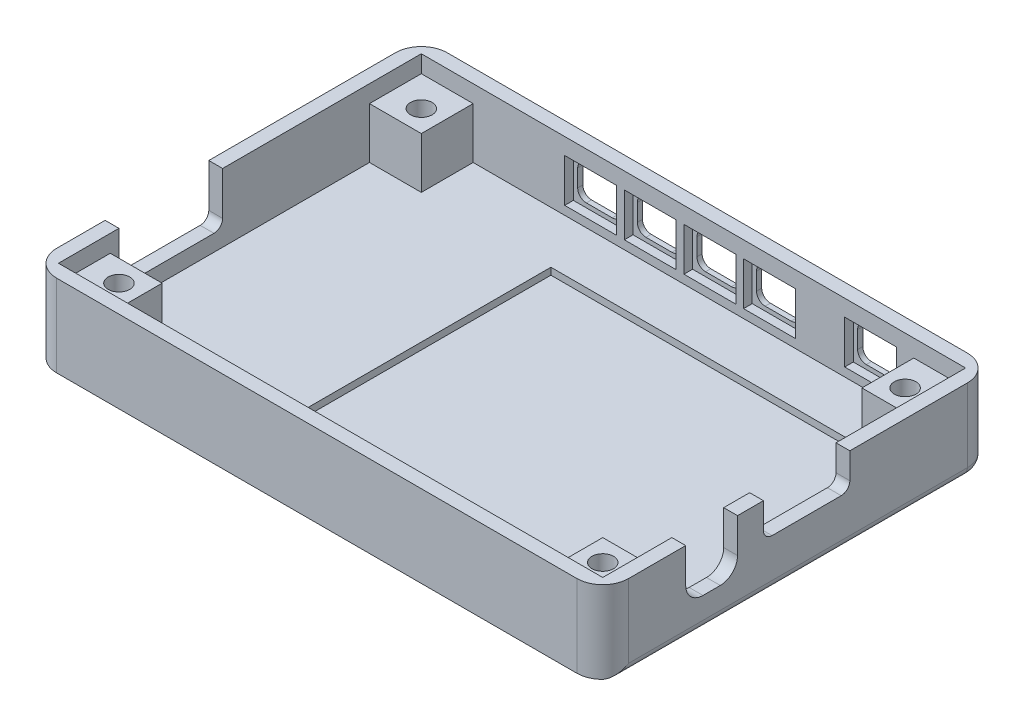
SolidWorks part; units mm, degrees
ref_plane "前视基准面" through (0, 0, 0) normal (0, 0, 1) x (1, 0, 0)
ref_plane "上视基准面" through (0, 0, 0) normal (0, 1, 0) x (1, 0, 0)
ref_plane "右视基准面" through (0, 0, 0) normal (1, 0, 0) x (0, 0, -1)
sketch "草图1" plane through (0, 0, 0) normal (0, 1, 0) x (1, 0, 0)
  line L1 (-31.5, -21) -> (31.5, -21)
  line L2 (-31.5, -21) -> (-31.5, 21)
  line L3 (-31.5, 21) -> (31.5, 21)
  line L4 (31.5, -21) -> (31.5, 21)
  line L5 (-31.5, -21) -> (31.5, 21) construction
  line L6 (-31.5, 21) -> (31.5, -21) construction
  point P0 (0, 0)
  dimension "D1" = 63
  dimension "D2" = 42
extrude "底" add sketch "草图1" against normal blind 1.6
sketch "草图2" plane through (0, 0, 0) normal (0, 1, 0) x (1, 0, 0)
  line L1 (-10.5, -15) -> (31.5, -15)
  line L2 (-10.5, -15) -> (-10.5, 15)
  line L3 (-10.5, 15) -> (31.5, 15)
  line L4 (31.5, -15) -> (31.5, 15)
  line L5 (-10.5, -15) -> (31.5, 15) construction
  line L6 (-10.5, 15) -> (31.5, -15) construction
  line L7 (31.5, 21) -> (-31.5, 21) construction
  line L8 (-31.5, -21) -> (31.5, -21) construction
  line L9 (31.5, -21) -> (31.5, 21) construction
  point P0 (0, 0)
  dimension "D1" = 42
  dimension "D2" = 6
  dimension "D3" = 0
  dimension "D4" = 6
extrude "电池槽" cut sketch "草图2" against normal blind 0.8
sketch "草图4" plane through (0, -1.6, 0) normal (0, -1, 0) x (-1, 0, 0)
  line L0 (-31.5, 21) -> (-31.5, -21)
  line L1 (-31.5, 21) -> (-33.1, 21)
  line L2 (-31.5, -21) -> (-33.1, -21)
  line L3 (-33.1, 21) -> (-33.1, -21)
  line L4 (31.5, 21) -> (31.5, -21)
  line L5 (31.5, 21) -> (33.1, 21)
  line L6 (31.5, -21) -> (33.1, -21)
  line L7 (33.1, 21) -> (33.1, -21)
  dimension "D1" = 1.6
  dimension "D2" = 1.6
extrude "侧边" add sketch "草图4" against normal blind 9.5
sketch "草图5" plane through (0, 0, 0) normal (0, 1, 0) x (1, 0, 0)
  line L0 (-31.5, 21) -> (-31.5, 15)
  line L1 (-31.5, 21) -> (-25.5, 21)
  line L2 (-31.5, 15) -> (-25.5, 15)
  line L3 (-25.5, 21) -> (-25.5, 15)
  line L4 (-31.5, 21) -> (-31.5, -21) construction
  line L5 (25.5, 21) -> (25.5, 15)
  line L6 (25.5, 21) -> (31.5, 21)
  line L7 (25.5, 15) -> (31.5, 15)
  line L8 (31.5, 21) -> (31.5, 15)
  line L9 (-31.5, -15) -> (-31.5, -21)
  line L10 (-31.5, -15) -> (-25.5, -15)
  line L11 (-31.5, -21) -> (-25.5, -21)
  line L12 (-25.5, -15) -> (-25.5, -21)
  line L13 (25.5, -15) -> (25.5, -21)
  line L14 (25.5, -15) -> (31.5, -15)
  line L15 (25.5, -21) -> (31.5, -21)
  line L16 (31.5, -15) -> (31.5, -21)
  dimension "D1" = 6
  dimension "D2" = 6
  dimension "D3" = 6
  dimension "D4" = 6
extrude "螺丝固定" add sketch "草图5" along normal offset from surface (5.9 mm away) 2 up to face at (-32.3, 7.9, 0)
sketch "草图6" plane through (0, 7.9, 0) normal (0, 1, 0) x (1, 0, 0)
  line L0 (-25.5, 15) -> (-25.5, 21) construction
  line L1 (-31.5, 15) -> (-25.5, 15) construction
  circle A0 centre (-28, 17.5) radius 1.25
  circle A1 centre (28, 17.5) radius 1.25
  circle A2 centre (28, -17.5) radius 1.25
  circle A3 centre (-28, -17.5) radius 1.25
  dimension "D1" = 2.5
  dimension "D2" = 2.5
  dimension "D3" = 2.5
  dimension "D4" = 2
  dimension "D5" = 2
extrude "螺丝孔" cut sketch "草图6" against normal up to surface (7.9 mm away) up to face at (-7, 0, 0)
sketch "草图8" plane through (0, 0, 0) normal (0, 1, 0) x (1, 0, 0)
  line L0 (25.5, 21) -> (25.5, 15) construction
  line L1 (-30.5, 20) -> (-25.5, 20)
  line L2 (-30.5, 20) -> (-30.5, 15)
  line L3 (-30.5, 15) -> (-25.5, 15)
  line L4 (-25.5, 20) -> (-25.5, 15)
  line L5 (-30.5, 20) -> (-25.5, 15) construction
  line L6 (-30.5, 15) -> (-25.5, 20) construction
  line L7 (30.5, 20) -> (25.5, 20)
  line L8 (30.5, 20) -> (30.5, 15)
  line L9 (30.5, 15) -> (25.5, 15)
  line L10 (25.5, 20) -> (25.5, 15)
  line L11 (30.5, 20) -> (25.5, 15) construction
  line L12 (30.5, 15) -> (25.5, 20) construction
  line L14 (-30.5, -20) -> (-25.5, -20)
  line L15 (-30.5, -20) -> (-30.5, -15)
  line L16 (-30.5, -15) -> (-25.5, -15)
  line L17 (-25.5, -20) -> (-25.5, -15)
  line L18 (-30.5, -20) -> (-25.5, -15) construction
  line L19 (-30.5, -15) -> (-25.5, -20) construction
  line L20 (30.5, -20) -> (25.5, -20)
  line L21 (30.5, -20) -> (30.5, -15)
  line L22 (30.5, -15) -> (25.5, -15)
  line L23 (25.5, -20) -> (25.5, -15)
  line L24 (30.5, -20) -> (25.5, -15) construction
  line L25 (30.5, -15) -> (25.5, -20) construction
  circle A0 centre (28, 17.5) radius 1.25 construction
  circle A1 centre (28, -17.5) radius 1.25 construction
  circle A2 centre (-28, -17.5) radius 1.25 construction
  circle A3 centre (-28, 17.5) radius 1.25 construction
  circle A4 centre (28, 17.5) radius 1.25 construction
  circle A5 centre (28, -17.5) radius 1.25 construction
  circle A6 centre (-28, -17.5) radius 1.25 construction
  circle A7 centre (-28, 17.5) radius 1.25 construction
sketch "草图9" plane through (0, 0, -21) normal (0, 0, -1) x (-1, 0, 0)
  line L0 (-33.1, 7.9) -> (-33.1, -1.6)
  line L1 (-33.1, 7.9) -> (33.1, 7.9)
  line L2 (-33.1, -1.6) -> (33.1, -1.6)
  line L3 (33.1, 7.9) -> (33.1, -1.6)
extrude "凸台-拉伸4" add sketch "草图9" along normal blind 1.6
sketch "草图10" plane through (0, 0, -21) normal (0, 0, 1) x (1, 0, 0)
  line L1 (17.5, 1) -> (23.5, 1)
  line L2 (17.5, 1) -> (17.5, 6)
  line L3 (17.5, 6) -> (23.5, 6)
  line L4 (23.5, 1) -> (23.5, 6)
  line L5 (17.5, 1) -> (23.5, 6) construction
  line L6 (17.5, 6) -> (23.5, 1) construction
  line L7 (25.5, 0) -> (-25.5, 0) construction
  line L8 (25.5, 5.9) -> (25.5, 0) construction
  line L9 (5.8, 1) -> (11.8, 1)
  line L10 (5.8, 1) -> (5.8, 6)
  line L11 (5.8, 6) -> (11.8, 6)
  line L12 (11.8, 1) -> (11.8, 6)
  line L13 (5.8, 1) -> (11.8, 6) construction
  line L14 (5.8, 6) -> (11.8, 1) construction
  line L15 (-1.1, 1) -> (4.9, 1)
  line L16 (-1.1, 1) -> (-1.1, 6)
  line L17 (-1.1, 6) -> (4.9, 6)
  line L18 (4.9, 1) -> (4.9, 6)
  line L19 (-1.1, 1) -> (4.9, 6) construction
  line L20 (-1.1, 6) -> (4.9, 1) construction
  line L21 (-8, 1) -> (-2, 1)
  line L22 (-8, 1) -> (-8, 6)
  line L23 (-8, 6) -> (-2, 6)
  line L24 (-2, 1) -> (-2, 6)
  line L25 (-8, 1) -> (-2, 6) construction
  line L26 (-8, 6) -> (-2, 1) construction
  line L27 (-14.9, 1) -> (-8.9, 1)
  line L28 (-14.9, 1) -> (-14.9, 6)
  line L29 (-14.9, 6) -> (-8.9, 6)
  line L30 (-8.9, 1) -> (-8.9, 6)
  line L31 (-14.9, 1) -> (-8.9, 6) construction
  line L32 (-14.9, 6) -> (-8.9, 1) construction
  point P0 (20.5, 3.5)
  point P11 (8.8, 3.5)
  point P16 (1.9, 3.5)
  point P21 (-5, 3.5)
  point P26 (-11.9, 3.5)
  dimension "D1" = 6
  dimension "D2" = 5
  dimension "D3" = 5
  dimension "D4" = 3.5
  dimension "D5" = 2
  dimension "D6" = 4
extrude "按键底" cut sketch "草图10" against normal blind 1
sketch "草图12" plane through (0, 0, -22) normal (0, 0, 1) x (1, 0, 0)
  line L0 (17.5, 6) -> (23.5, 1) construction
  line L1 (6.3, 2.5) -> (6.3, 4.5)
  line L2 (19, 1.5) -> (22, 1.5)
  line L3 (18, 2.5) -> (18, 4.5)
  line L4 (23.5, 1) -> (23.5, 6)
  line L5 (23.5, 6) -> (17.5, 6)
  line L6 (17.5, 6) -> (17.5, 1)
  line L7 (17.5, 1) -> (23.5, 1)
  line L8 (23.5, 1) -> (23.5, 6) construction
  line L9 (23.5, 6) -> (17.5, 6) construction
  line L10 (17.5, 6) -> (17.5, 1) construction
  line L11 (17.5, 1) -> (23.5, 1) construction
  line L12 (19, 5.5) -> (22, 5.5)
  line L13 (23, 2.5) -> (23, 4.5)
  line L14 (18, 1.5) -> (23, 5.5) construction
  line L15 (18, 5.5) -> (23, 1.5) construction
  line L16 (7.3, 1.5) -> (10.3, 1.5)
  line L17 (7.3, 5.5) -> (10.3, 5.5)
  line L18 (11.3, 2.5) -> (11.3, 4.5)
  line L19 (-0.6, 2.5) -> (-0.6, 4.5)
  line L20 (0.4, 1.5) -> (3.4, 1.5)
  line L21 (0.4, 5.5) -> (3.4, 5.5)
  line L22 (4.4, 2.5) -> (4.4, 4.5)
  line L23 (-7.5, 2.5) -> (-7.5, 4.5)
  line L24 (-6.5, 1.5) -> (-3.5, 1.5)
  line L25 (-6.5, 5.5) -> (-3.5, 5.5)
  line L26 (-2.5, 2.5) -> (-2.5, 4.5)
  line L27 (-14.4, 2.5) -> (-14.4, 4.5)
  line L28 (-13.4, 1.5) -> (-10.4, 1.5)
  line L29 (-13.4, 5.5) -> (-10.4, 5.5)
  line L30 (-9.4, 2.5) -> (-9.4, 4.5)
  arc A0 (22, 5.5) -> (23, 4.5) centre (22, 4.5) cw
  arc A1 (22, 1.5) -> (23, 2.5) centre (22, 2.5) ccw
  arc A2 (19, 1.5) -> (18, 2.5) centre (19, 2.5) cw
  arc A3 (18, 4.5) -> (19, 5.5) centre (19, 4.5) cw
  arc A4 (6.3, 4.5) -> (7.3, 5.5) centre (7.3, 4.5) cw
  arc A5 (7.3, 1.5) -> (6.3, 2.5) centre (7.3, 2.5) cw
  arc A6 (10.3, 5.5) -> (11.3, 4.5) centre (10.3, 4.5) cw
  arc A7 (10.3, 1.5) -> (11.3, 2.5) centre (10.3, 2.5) ccw
  arc A8 (-0.6, 4.5) -> (0.4, 5.5) centre (0.4, 4.5) cw
  arc A9 (0.4, 1.5) -> (-0.6, 2.5) centre (0.4, 2.5) cw
  arc A10 (3.4, 5.5) -> (4.4, 4.5) centre (3.4, 4.5) cw
  arc A11 (3.4, 1.5) -> (4.4, 2.5) centre (3.4, 2.5) ccw
  arc A12 (-7.5, 4.5) -> (-6.5, 5.5) centre (-6.5, 4.5) cw
  arc A13 (-6.5, 1.5) -> (-7.5, 2.5) centre (-6.5, 2.5) cw
  arc A14 (-3.5, 5.5) -> (-2.5, 4.5) centre (-3.5, 4.5) cw
  arc A15 (-3.5, 1.5) -> (-2.5, 2.5) centre (-3.5, 2.5) ccw
  arc A16 (-14.4, 4.5) -> (-13.4, 5.5) centre (-13.4, 4.5) cw
  arc A17 (-13.4, 1.5) -> (-14.4, 2.5) centre (-13.4, 2.5) cw
  arc A18 (-10.4, 5.5) -> (-9.4, 4.5) centre (-10.4, 4.5) cw
  arc A19 (-10.4, 1.5) -> (-9.4, 2.5) centre (-10.4, 2.5) ccw
  point P2 (20.5, 3.5)
  dimension "D4" = 1
  dimension "D2" = 5
  dimension "D3" = 4
  dimension "D1" = 0
  dimension "D5" = 2
  dimension "D6" = 4
extrude "按键头" cut sketch "草图12" against normal up to next
fillet "圆角4" radius 1 3 edges at (-33.1, -1.6, -0.8) (33.1, -1.6, -0.8) (0, -1.6, -22.6)
fillet "圆角5" radius 3 4 edges at (-32.8071, -1.3071, -22.3071) (32.8071, -1.3071, -22.3071) (33.1, 3.65, -22.6) (-33.1, 3.65, -22.6)
sketch "草图15" plane through (0, 7.9, 0) normal (0, 1, 0) x (1, 0, 0)
  line L16 (33.1, -21) -> (33.1, 19.6)
  line L17 (30.1, 22.6) -> (-30.1, 22.6)
  line L18 (-33.1, 19.6) -> (-33.1, -21)
  line L19 (-33.1, -21) -> (-31.5, -21)
  line L22 (-31.5, -21) -> (-31.5, 21)
  line L25 (-31.5, 21) -> (31.5, 21)
  line L28 (31.5, 21) -> (31.5, -21)
  line L31 (31.5, -21) -> (33.1, -21)
  line L32 (33.1, -21) -> (33.1, 19.6)
  line L33 (30.1, 22.6) -> (-30.1, 22.6)
  line L34 (-33.1, 19.6) -> (-33.1, -21)
  line L35 (-33.1, -21) -> (-31.5, -21)
  line L38 (-31.5, -21) -> (-31.5, 21)
  line L41 (-31.5, 21) -> (31.5, 21)
  line L44 (31.5, 21) -> (31.5, -21)
  line L47 (31.5, -21) -> (33.1, -21)
  arc A2 (33.1, 19.6) -> (30.1, 22.6) centre (30.1, 19.6) ccw
  arc A3 (-30.1, 22.6) -> (-33.1, 19.6) centre (-30.1, 19.6) ccw
  arc A4 (33.1, 19.6) -> (30.1, 22.6) centre (30.1, 19.6) ccw
  arc A5 (-30.1, 22.6) -> (-33.1, 19.6) centre (-30.1, 19.6) ccw
  dimension "D1" = 0
sketch "草图16" plane through (-31.5, 0, 0) normal (1, 0, 0) x (0, 0, -1)
  line L0 (-14, 7.9) -> (-2, 7.9)
  line L1 (-14, 7.9) -> (-14, 2.9)
  line L2 (-2, 7.9) -> (-2, 2.9)
  line L3 (-13, 1.9) -> (-3, 1.9)
  line L4 (-21, 7.9) -> (21, 7.9) construction
  line L5 (-15, 5.9) -> (-15, 0) construction
  arc A0 (-14, 2.9) -> (-13, 1.9) centre (-13, 2.9) ccw
  arc A1 (-2, 2.9) -> (-3, 1.9) centre (-3, 2.9) cw
  point P10 (-14, 1.9)
  point P13 (-2, 1.9)
  dimension "D4" = 1
  dimension "D1" = 12
  dimension "D2" = 6
  dimension "D3" = 1
extrude "tf口" cut sketch "草图16" against normal up to next
sketch "草图17" plane through (31.5, 0, 0) normal (-1, 0, 0) x (0, 0, 1)
  line L0 (7, 7.9) -> (13, 7.9)
  line L1 (7, 7.9) -> (7, 3.9)
  line L2 (13, 7.9) -> (13, 3.9)
  line L3 (9, 1.9) -> (11, 1.9)
  line L4 (-21, 7.9) -> (21, 7.9) construction
  line L5 (15, -0.8) -> (15, 5.9) construction
  line L6 (4, 7.9) -> (-6, 7.9)
  line L7 (4, 7.9) -> (4, 4.9)
  line L8 (-6, 7.9) -> (-6, 4.9)
  line L9 (3, 3.9) -> (-5, 3.9)
  line L11 (21, 7.9) -> (-21, 7.9) construction
  arc A0 (13, 3.9) -> (11, 1.9) centre (11, 3.9) cw
  arc A1 (7, 3.9) -> (9, 1.9) centre (9, 3.9) ccw
  arc A2 (4, 4.9) -> (3, 3.9) centre (3, 4.9) cw
  arc A3 (-6, 4.9) -> (-5, 3.9) centre (-5, 4.9) ccw
  point P10 (13, 1.9)
  point P13 (7, 1.9)
  point P22 (4, 3.9)
  point P25 (-6, 3.9)
  dimension "D4" = 2
  dimension "D8" = 1
  dimension "D1" = 6
  dimension "D2" = 6
  dimension "D3" = 2
  dimension "D5" = 10
  dimension "D6" = 11
  dimension "D7" = 4
extrude "切除-拉伸1" cut sketch "草图17" against normal up to next
sketch "草图18" plane through (0, 0, 21) normal (0, 0, 1) x (1, 0, 0)
  line L0 (33.1, 7.9) -> (33.1, -0.6) construction
  line L1 (-32.1, -1.6) -> (32.1, -1.6) construction
  line L2 (-33.1, 7.9) -> (-33.1, -0.6) construction
  line L3 (33.1, 7.9) -> (33.1, -0.6)
  line L4 (-32.1, -1.6) -> (32.1, -1.6)
  line L5 (-33.1, 7.9) -> (-33.1, -0.6)
  line L6 (-33.1, 7.9) -> (33.1, 7.9)
  arc A0 (32.1, -1.6) -> (33.1, -0.6) centre (32.1, -0.6) ccw construction
  arc A1 (-33.1, -0.6) -> (-32.1, -1.6) centre (-32.1, -0.6) ccw construction
  arc A2 (32.1, -1.6) -> (33.1, -0.6) centre (32.1, -0.6) ccw
  arc A3 (-33.1, -0.6) -> (-32.1, -1.6) centre (-32.1, -0.6) ccw
extrude "封底" add sketch "草图18" along normal blind 1.6
fillet "圆角7" radius 3 2 edges at (33.1, 3.65, 22.6) (-33.1, 3.65, 22.6) tangent propagation no
